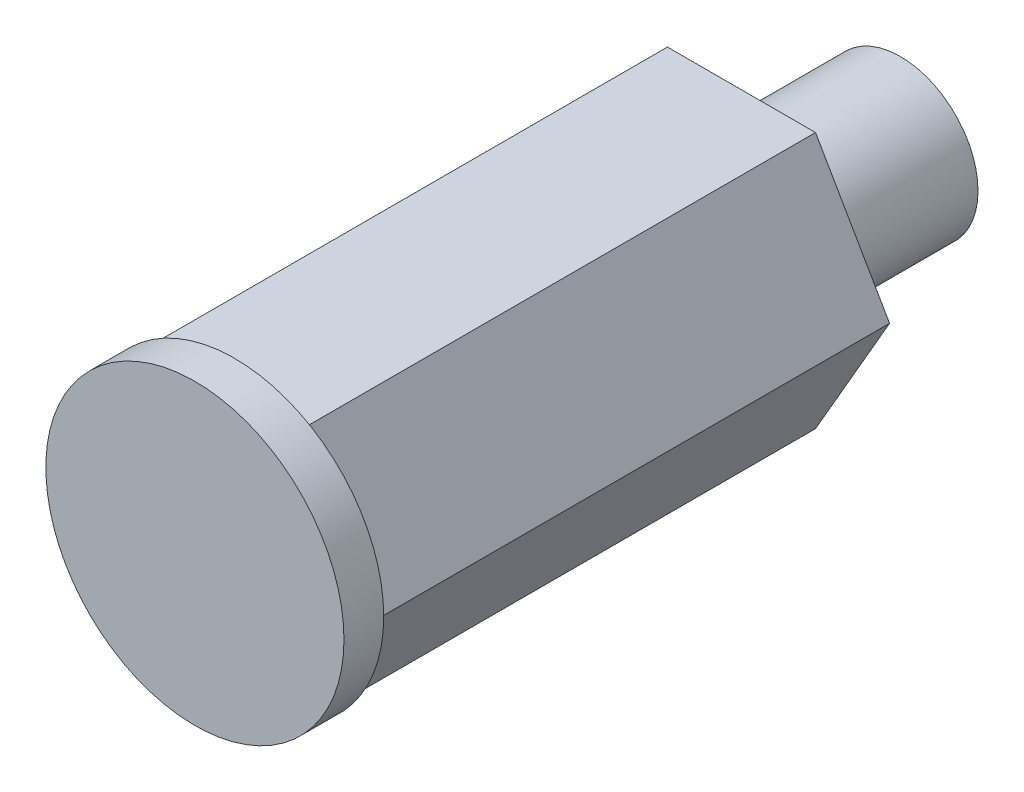
SolidWorks part; units mm, degrees
ref_plane "Front Plane" through (0, 0, 0) normal (0, 0, 1) x (1, 0, 0)
ref_plane "Top Plane" through (0, 0, 0) normal (0, 1, 0) x (1, 0, 0)
ref_plane "Right Plane" through (0, 0, 0) normal (1, 0, 0) x (0, 0, -1)
sketch "Sketch1" plane through (0, 0, 0) normal (0, 0, 1) x (1, 0, 0)
  line L0 (-1.9442, -2.015) -> (-1.9442, 2.015)
  line L1 (-1.9442, -2.015) -> (1.9442, -2.015) construction
  line L2 (-1.9442, -2.015) -> (-1.9442, 2.015) construction
  line L3 (-1.9442, 2.015) -> (1.9442, 2.015) construction
  line L4 (1.9442, -2.015) -> (1.9442, 2.015) construction
  line L5 (-1.9442, -2.015) -> (1.9442, 2.015) construction
  line L6 (-1.9442, 2.015) -> (1.9442, -2.015) construction
  line L7 (1.9442, -2.015) -> (1.9442, 2.015)
  circle A0 centre (0, 0) radius 2.8 construction
  arc A1 (-1.9442, 2.015) -> (1.9442, 2.015) centre (0, 0) cw
  arc A2 (-1.9442, -2.015) -> (1.9442, -2.015) centre (0, 0) ccw
  circle A3 centre (0, 0) radius 3.9
  dimension "D1" = 5.6
  dimension "D3" = 7.8
  dimension "D2" = 4.03
extrude "Boss-Extrude1" add sketch "Sketch1" along normal blind 8
sketch "Sketch2" plane through (0, 0, 8) normal (0, 0, 1) x (1, 0, 0)
  line L7 (3.725, 6.4519) -> (-3.725, 6.4519)
  line L8 (-3.725, 6.4519) -> (-7.45, 0)
  line L9 (-7.45, 0) -> (-3.725, -6.4519)
  line L10 (-3.725, -6.4519) -> (3.725, -6.4519)
  line L11 (3.725, -6.4519) -> (7.45, 0)
  line L12 (7.45, 0) -> (3.725, 6.4519)
  circle A0 centre (0, 0) radius 6.4519 construction
  point P1 (0, 6.4519)
  dimension "D1" = 7.45
extrude "Boss-Extrude2" add sketch "Sketch2" along normal blind 25.5 contours L7 L8 L9 L10 L11 L12
sketch "Sketch3" plane through (0, 0, 33.5) normal (0, 0, 1) x (1, 0, 0)
  circle A0 centre (0, 0) radius 7.5
  dimension "D1" = 15
extrude "Boss-Extrude3" add sketch "Sketch3" along normal blind 2
